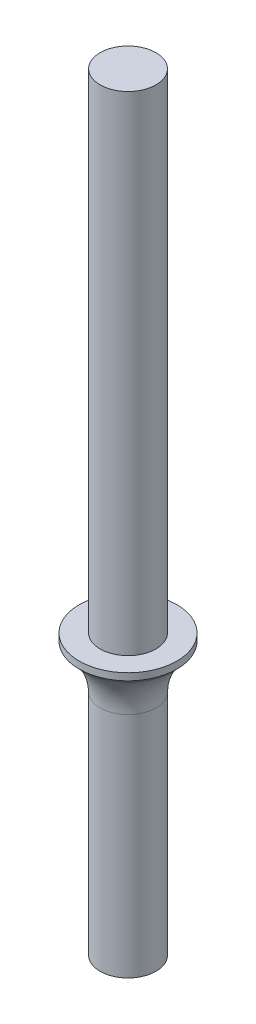
SolidWorks part; units mm, degrees
material "PVC 0.007 Plasticized"
ref_plane "Front Plane" through (0, 0, 0) normal (0, 0, 1) x (1, 0, 0)
ref_plane "Top Plane" through (0, 0, 0) normal (0, 1, 0) x (1, 0, 0)
ref_plane "Right Plane" through (0, 0, 0) normal (1, 0, 0) x (0, 0, -1)
sketch "Sketch1" plane through (0, 0, 0) normal (0, 1, 0) x (1, 0, 0)
  circle A0 centre (0, 0) radius 4
  dimension "D1" = 8
extrude "Boss-Extrude1" add sketch "Sketch1" along normal blind 110
ref_plane "Plane1" through (0, 55, 0) normal (0, 1, 0) x (1, 0, 0)
ref_plane "Plane2" through (0, 39, 0) normal (0, -1, 0) x (-1, 0, 0)
sketch "Sketch2" plane through (0, 39, 0) normal (0, -1, 0) x (-1, 0, 0)
  circle A0 centre (0, 0) radius 7
  circle A1 centre (0, 0) radius 4 construction
  dimension "D1" = 3
extrude "Boss-Extrude2" add sketch "Sketch2" against normal blind 1
chamfer "Chamfer1" distance 3 angle 45 1 edges at (0, 39, -4)
fillet "Fillet1" radius 8 1 edges at (0, 36, -4)
